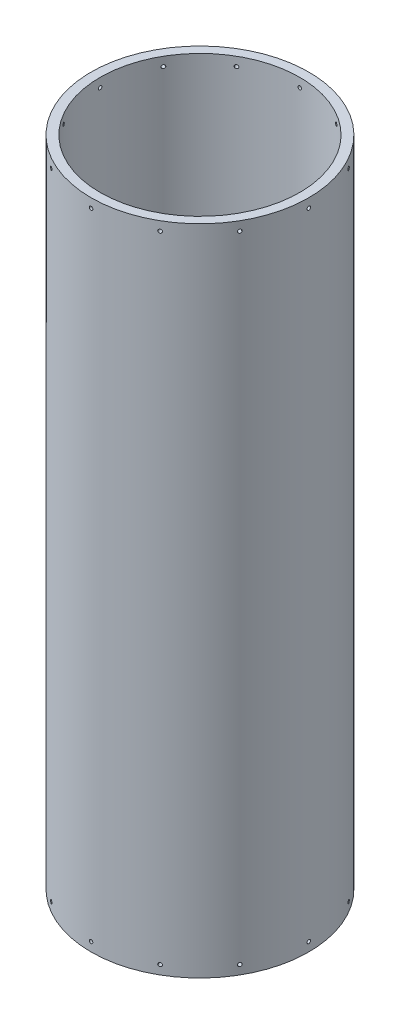
SolidWorks part; units mm, degrees
ref_plane "Front Plane" through (0, 0, 0) normal (0, 0, 1) x (1, 0, 0)
ref_plane "Top Plane" through (0, 0, 0) normal (0, 1, 0) x (1, 0, 0)
ref_plane "Right Plane" through (0, 0, 0) normal (1, 0, 0) x (0, 0, -1)
sketch "Sketch1" plane through (0, 0, 0) normal (0, 1, 0) x (1, 0, 0)
  circle A0 centre (0, 0) radius 152.4
  circle A1 centre (0, 0) radius 139.7
  dimension "D2" = 304.8
  dimension "D1" = 279.4
extrude "Boss-Extrude1" add sketch "Sketch1" along normal blind 914.4
ref_plane "Plane1" through (-152.4, 0, 0) normal (-1, 0, 0) x (0, 0, 1)
hole_wizard "#10 (0.1935) Diameter Hole1" positions "Sketch2" profile "Sketch3" hole size "#10" standard "ANSI Inch" end condition up to next
sketch "Sketch2" plane through (-152.4, 0, 0) normal (-1, 0, 0) x (0, 0, 1)
  line L0 (0, -167.64) -> (0, 167.64) construction
  line L1 (152.4, 914.4) -> (-152.4, 914.4) construction
  point P0 (0, 901.7)
  dimension "D1" = 12.7
sketch "Sketch3" plane through (-152.4, 901.7, 0) normal (0, 1, 0) x (0, 0, 1)
  line L0 (0, 0) -> (0, 343.2351)
  line L1 (0, 343.2351) -> (2.4574, 343.2351)
  line L2 (2.4574, 343.2351) -> (2.4574, 0)
  line L5 (2.4574, 0) -> (0, 0)
  line L11 (0, -6.35) -> (0, 107.95) construction
  dimension "Thru Hole Dia." = 4.9149
  dimension "Thru Hole Depth" = 343.2351
pattern_circular "CirPattern1" count 12 over 360 about axis through (0, 914.4, 0) along (0, 1, 0) of "#10 (0.1935) Diameter Hole1"
ref_plane "Plane2" through (0, 457.2, 0) normal (0, 1, 0) x (1, 0, 0)
mirror "Mirror1" about plane through (0, 457.2, 0) normal (0, 1, 0) of "CirPattern1"
